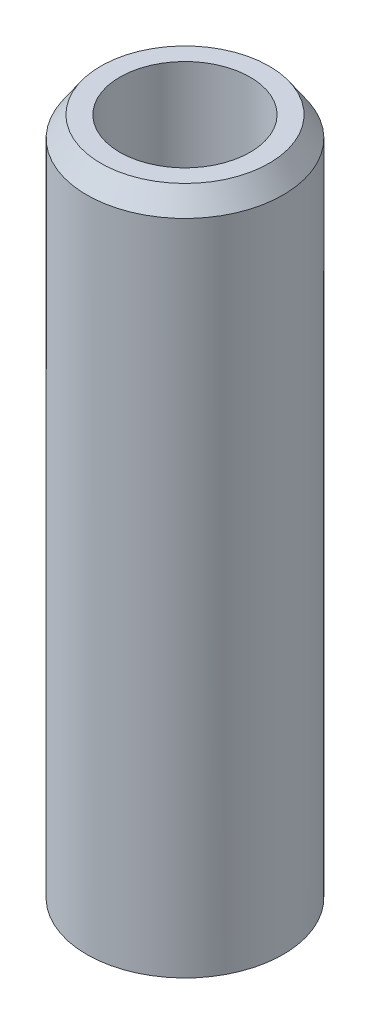
SolidWorks part; units mm, degrees
ref_plane "Front Plane" through (0, 0, 0) normal (0, 0, 1) x (1, 0, 0)
ref_plane "Top Plane" through (0, 0, 0) normal (0, 1, 0) x (1, 0, 0)
ref_plane "Right Plane" through (0, 0, 0) normal (1, 0, 0) x (0, 0, -1)
sketch "Sketch1" plane through (0, 0, 0) normal (0, 1, 0) x (1, 0, 0)
  circle A0 centre (0, 0) radius 22.5
  dimension "SHAFT_OD" = 45
extrude "Boss-Extrude1" add sketch "Sketch1" along normal blind 158.5959
sketch "Sketch2" plane through (0, 0, 0) normal (0, 1, 0) x (1, 0, 0)
  circle A0 centre (0, 0) radius 14.9268
  dimension "BORE_D" = 29.8537
extrude "Cut-Extrude1" cut sketch "Sketch2" along normal through all
chamfer "Chamfer1" distance 4.6821 angle 34.398 2 edges at (0, 158.5959, 22.5) (0, 0, 22.5) first distance on face at (0, 158.5959, 22.5) first distance on face at (0, 0, 14.9268)
